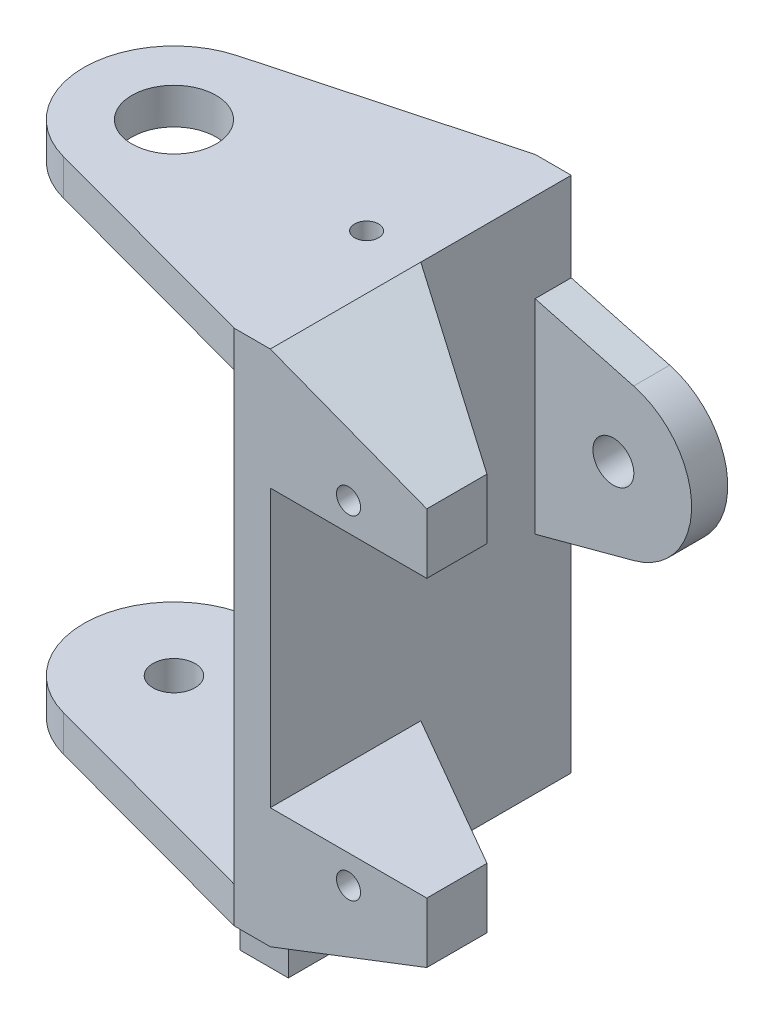
SolidWorks part; units mm, degrees
ref_plane "Plano frontal" through (0, 0, 0) normal (0, 0, 1) x (1, 0, 0)
ref_plane "Plano superior" through (0, 0, 0) normal (0, 1, 0) x (1, 0, 0)
ref_plane "Plano direito" through (0, 0, 0) normal (1, 0, 0) x (0, 0, -1)
sketch "Esboço1" plane through (0, 0, 0) normal (0, 0, 1) x (1, 0, 0)
  line L1 (0, -21.5) -> (-33, -21.5)
  line L2 (-33, -21.5) -> (-33, -18.5)
  line L3 (-33, -18.5) -> (-3, -18.5)
  line L4 (-3, -18.5) -> (-3, 18.5)
  line L5 (-3, 18.5) -> (-33, 18.5)
  line L6 (-33, 18.5) -> (-33, 21.5)
  line L7 (-33, 21.5) -> (0, 21.5)
  line L8 (0, 21.5) -> (13, 16.5)
  line L9 (13, 16.5) -> (13, 11.5)
  line L10 (13, 11.5) -> (0, 11.5)
  line L11 (0, -21.5) -> (13, -16.5)
  line L12 (13, -16.5) -> (13, -11.5)
  line L13 (13, -11.5) -> (0, -11.5)
  line L14 (0, 11.5) -> (0, -11.5)
  line L17 (0, 0) -> (31.9596, 0) construction
  circle A0 centre (6.5, 13.85) radius 1
  circle A2 centre (6.5, -13.85) radius 1
  point P4 (0, 0)
  point P7 (13, 21.5)
  point P12 (13, 15.8255)
  point P19 (0, 0)
  point P20 (-3, 0)
  point P23 (6.5, 11.5)
  dimension "D9" = 2
  dimension "D1" = 23
  dimension "D2" = 3
  dimension "D3" = 13
  dimension "D4" = 5
  dimension "D5" = 3
  dimension "D6" = 37
  dimension "D7" = 30
  dimension "D10" = 27.7
extrude "Ressalto-extrusão1" add sketch "Esboço1" along normal mid plane 25
sketch "Esboço2" plane through (0, 21.5, 0) normal (0, 1, 0) x (1, 0, 0)
  line L0 (-33, -12.5) -> (-33, 12.5) construction
  line L2 (0, 0) -> (-3.8141, 0) construction
  line L3 (-3, 12.5) -> (-22.4572, 7.2401)
  line L6 (13, 12.5) -> (0, 12.5) construction
  line L7 (-3, 12.5) -> (-3, -12.5) construction
  line L8 (13, -12.5) -> (0, -12.5) construction
  line L9 (-3, -12.5) -> (-22.4572, -7.2401)
  line L10 (-3, 12.5) -> (-33, 12.5)
  line L11 (-33, 12.5) -> (-33, -12.5)
  line L12 (-33, -12.5) -> (-3, -12.5)
  line L13 (-33, -12.5) -> (-33, 12.5) construction
  circle A0 centre (-20.5, 0) radius 3.5
  circle A1 centre (-4.5, 0) radius 1
  arc A2 (-22.4572, 7.2401) -> (-22.4572, -7.2401) centre (-20.5, 0) ccw
  point P4 (-33, -12.5)
  point P10 (-33, 0)
  point P23 (0, 0)
  line M3 (0, 12.5) -> (-33, 12.5)
  line M4 (-33, 12.5) -> (-33, -12.5)
  line M5 (-33, -12.5) -> (0, -12.5)
  dimension "D1" = 7
  dimension "D3" = 2
  dimension "D2" = 16
  dimension "D5" = 15
  dimension "D4" = 12.5
  dimension "D6" = 16
extrude "Corte-extrusão1" cut sketch "Esboço2" against normal blind 15
sketch "Esboço4" plane through (0, -11.5, 0) normal (0, 1, 0) x (1, 0, 0)
  line L0 (13, -12.5) -> (13, 12.5) construction
  line L1 (13, -7.5) -> (0, 0.0056)
  line L2 (13, -7.5) -> (13, 12.5)
  line L3 (13, 12.5) -> (0, 12.5)
  line L4 (0, 0.0056) -> (0, 12.5)
  line L6 (0, -12.5) -> (0, 12.5) construction
  point P9 (0, -5.5)
  dimension "D1" = 5
  dimension "D2" = 60
extrude "Corte-extrusão2" cut sketch "Esboço4" against normal through all both and the other way through all
sketch "Esboço5" plane through (0, 0, -12.5) normal (0, 0, -1) x (-1, 0, 0)
  line L0 (-6.5, 13.85) -> (-6.5, -13.85) construction
  line L1 (-8.1823, 11.9285) -> (0, 14.121)
  line L2 (0, -11.5) -> (0, 11.5) construction
  line L3 (-8.1823, -0.6285) -> (0, -2.821)
  line L4 (0, 14.121) -> (0, -2.821)
  line L7 (-13, 11.5) -> (-13, 16.5) construction
  arc A0 (-8.1823, 11.9285) -> (-8.1823, -0.6285) centre (-6.5, 5.65) ccw
  circle A1 centre (-6.5, 5.65) radius 1.7
  point P16 (-6.5, 0)
  dimension "D1" = 3.4
  dimension "D3" = 5.65
  dimension "D2" = 75
extrude "Ressalto-extrusão2" add sketch "Esboço5" against normal blind 3
sketch "Esboço7" plane through (0, -18.5, 0) normal (0, 1, 0) x (1, 0, 0)
  circle A0 centre (-20.5, 0) radius 1.75
  dimension "D1" = 3.5
extrude "Corte-extrusão3" cut sketch "Esboço7" against normal blind 10
extrude "Corte-extrusão4" cut sketch "Esboço2<2>" against normal through all contours M4 | A2 L3 L9 M3 M4 M5 region at (-12.8305, 21.5, -10.247)
sketch "Esboço2<2>" plane through (0, 21.5, 0) normal (0, 1, 0) x (1, 0, 0) same geometry as "Esboço2"
sketch "Esboço8" plane through (0, 0, 0) normal (1, 0, 0) x (0, 0, -1)
  line L0 (0, 0) -> (0, -11.3279) construction
  line L2 (-1.6213, -28.5) -> (-1.6213, -25.5) construction
  line L3 (1.7574, -25.5) -> (3.8787, -27.6213) construction
  line L4 (10, -21.5) -> (3, -28.5)
  line L5 (3, -28.5) -> (-7, -28.5)
  line L6 (-7, -28.5) -> (-7, -25.5)
  line L7 (-7, -25.5) -> (-5, -24)
  line L8 (-5, -24) -> (-5, -25.5)
  line L9 (-5, -25.5) -> (1.7574, -25.5)
  line L10 (12.5, 0) -> (-12.5, 0) construction
  line L11 (12.5, 18.5) -> (12.5, -18.5) construction
  line L12 (-12.5, 18.5) -> (-12.5, -18.5) construction
  line L13 (1.7574, -25.5) -> (5.7574, -21.5)
  line L24 (5.7574, -21.5) -> (10, -21.5)
extrude "Ressalto-extrusão3" add sketch "Esboço8" against normal blind 4 from offset 4 offset against normal yes
